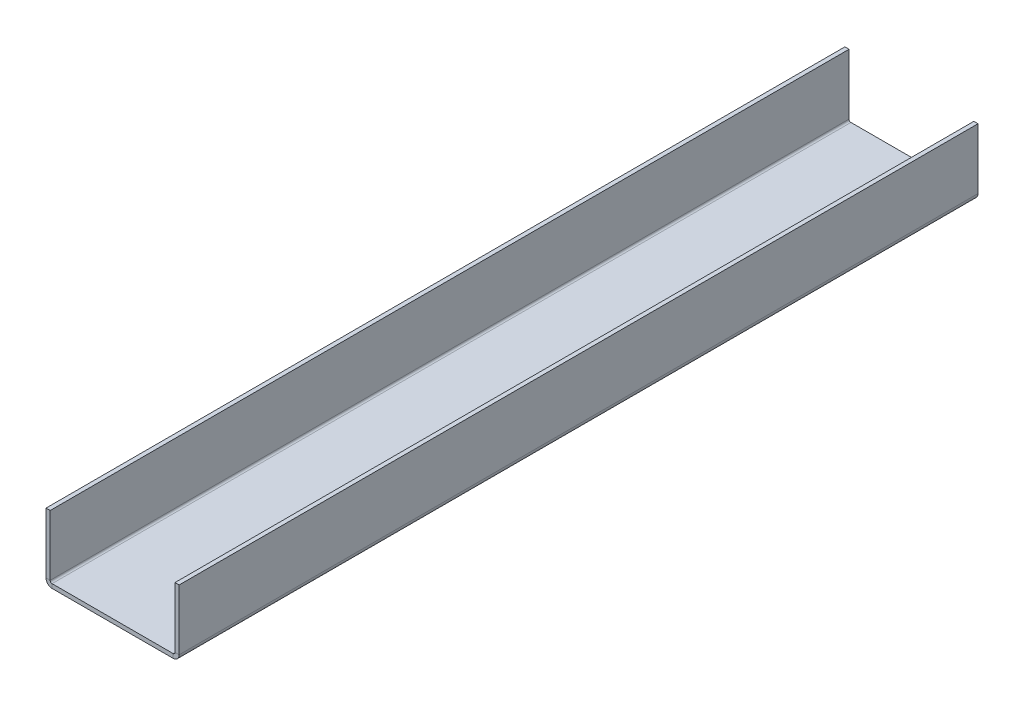
SolidWorks part; units mm, degrees
note: The reader was unsure of these and kept them because the rebuilt part matched: flange length of "Edge-Flange1", "Edge-Flange2".
ref_plane "Front Plane" through (0, 0, 0) normal (0, 0, 1) x (1, 0, 0)
ref_plane "Top Plane" through (0, 0, 0) normal (0, 1, 0) x (1, 0, 0)
ref_plane "Right Plane" through (0, 0, 0) normal (1, 0, 0) x (0, 0, -1)
sketch "Sketch1" plane through (0, 0, 0) normal (0, 1, 0) x (1, 0, 0)
  line L1 (-25.4, 152.4) -> (25.4, 152.4)
  line L2 (-25.4, 152.4) -> (-25.4, -152.4)
  line L3 (-25.4, -152.4) -> (25.4, -152.4)
  line L4 (25.4, 152.4) -> (25.4, -152.4)
  dimension "D1" = 50.8
  dimension "D2" = 304.8
  dimension "D3" = 152.4
  dimension "D4" = 25.4
base flange "Base-Flange1" sketch "Sketch1" thickness 1.5875 reverse thickness direction no parameters "D1"=0.7366
edge flange "Edge-Flange1" sketch "Sketch10" flange angle 90 flange length 25.4 flange position material inside bend radius 0.7366 thickness 1.5875 relief rectangular parameters "D6"=10
sketch "Sketch10" plane through (25.4, 0, 0) normal (1, 0, 0) x (0, 0, -1)
  line L2 (-152.4, 0) -> (-152.4, 23.8125)
  line L3 (-152.4, 23.8125) -> (152.4, 23.8125)
  line L4 (152.4, 23.8125) -> (152.4, 0)
  line L5 (-152.4, 0) -> (152.4, 0) construction
  line L6 (-152.4, 0) -> (152.4, 0)
bend "EdgeBend1" bend radius 0.7366 bend angle 90 parameters "D5"=1
edge flange "Edge-Flange2" sketch "Sketch13" flange angle 90 flange length 25.4 flange position material inside bend radius 0.7366 thickness 1.5875 relief rectangular parameters "D6"=10
sketch "Sketch13" plane through (-25.4, 0, 0) normal (-1, 0, 0) x (0, 0, 1)
  line L0 (-152.4, 0) -> (152.4, 0) construction
  line L1 (-152.4, 0) -> (152.4, 0)
  line L2 (-152.4, 0) -> (-152.4, 23.8125)
  line L3 (-152.4, 23.8125) -> (152.4, 23.8125)
  line L4 (152.4, 23.8125) -> (152.4, 0)
bend "EdgeBend2" bend radius 0.7366 bend angle 90 parameters "D5"=2
sketch "Bend-Lines1" plane through (0, 0, 0) normal (0, 1, 0) x (1, 0, 0)
sketch "Bounding-Box1" plane through (0, 0, 0) normal (0, 1, 0) x (1, 0, 0)
sheet metal parameters "Sheet-Metal1" thickness 1.5875 parameters "D1"=0.7366
flat pattern "Flat-Pattern1" [suppressed]
sketch "Bend-Lines2" plane through (0, 0, 0) normal (0, 1, 0) x (1, 0, 0)
sketch "Bounding-Box2" [suppressed] plane through (0, 0, 0) normal (0, 1, 0) x (1, 0, 0)
sheet metal parameters "Sheet-Metal2" thickness 1.5875 parameters "D1"=0.7366
flat pattern "Flat-Pattern1" [suppressed]
sketch "Bend-Lines2" plane through (0, 0, 0) normal (0, 1, 0) x (1, 0, 0)
sketch "Bounding-Box2" [suppressed] plane through (0, 0, 0) normal (0, 1, 0) x (1, 0, 0)
bend of the flat pattern "Flatten-<EdgeBend1>1"
sheet metal parameters "Sheet-Metal3" thickness 1.5875 parameters "D1"=0.7366
flat pattern "Flat-Pattern1" [suppressed]
sketch "Bend-Lines2" plane through (0, 0, 0) normal (0, 1, 0) x (1, 0, 0)
sketch "Bounding-Box2" [suppressed] plane through (0, 0, 0) normal (0, 1, 0) x (1, 0, 0)
bend of the flat pattern "Flatten-<EdgeBend1>1"
bend of the flat pattern "Flatten-<EdgeBend2>1"
